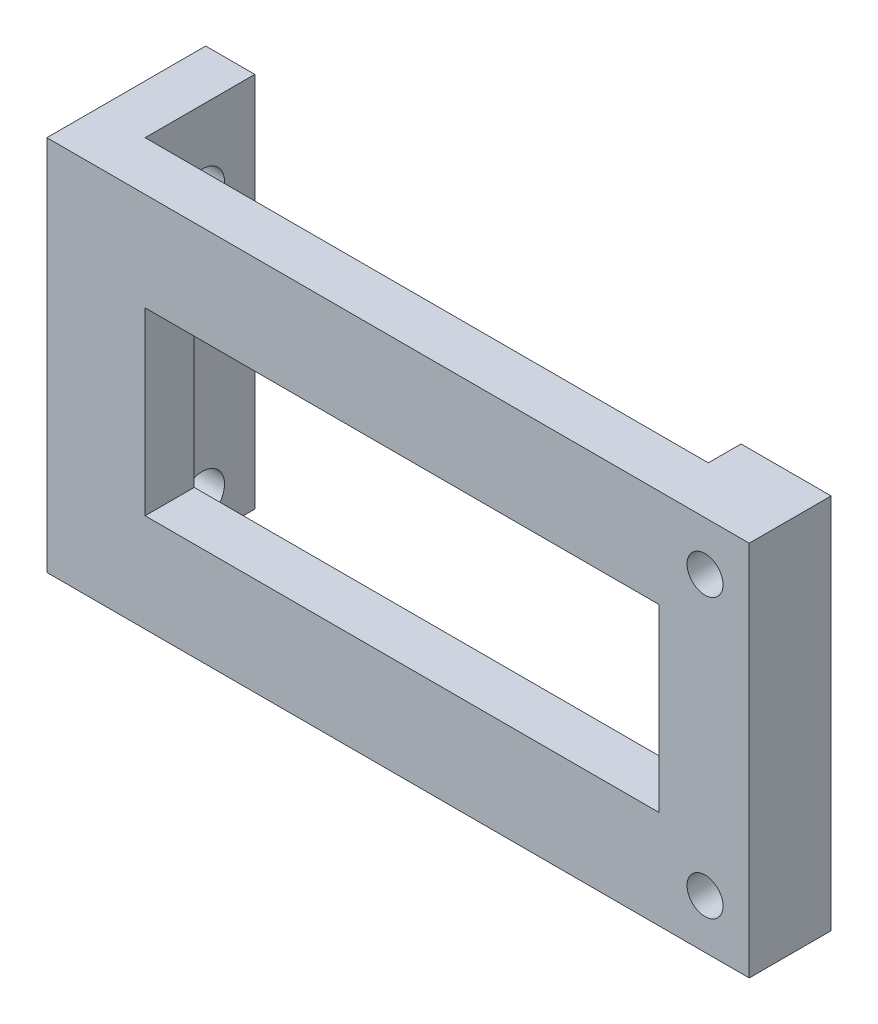
SolidWorks part; units mm, degrees
ref_plane "Front Plane" through (0, 0, 0) normal (0, 0, 1) x (1, 0, 0)
ref_plane "Top Plane" through (0, 0, 0) normal (0, 1, 0) x (1, 0, 0)
ref_plane "Right Plane" through (0, 0, 0) normal (1, 0, 0) x (0, 0, -1)
sketch "Sketch1" plane through (0, 0, 0) normal (0, 0, 1) x (1, 0, 0)
  line L0 (-15.45, 11.5) -> (-15.45, 5.5) construction
  line L1 (21.45, 11.5) -> (-21.45, 11.5)
  line L2 (21.45, 11.5) -> (21.45, -11.5)
  line L3 (21.45, -11.5) -> (-21.45, -11.5)
  line L4 (-21.45, 11.5) -> (-21.45, -11.5)
  line L5 (21.45, 11.5) -> (-21.45, -11.5) construction
  line L6 (21.45, -11.5) -> (-21.45, 11.5) construction
  line L7 (-21.45, 11.5) -> (-18.45, 11.5)
  line L8 (-21.45, 11.5) -> (-21.45, -11.5)
  line L9 (-21.45, -11.5) -> (-18.45, -11.5)
  line L10 (-18.45, 11.5) -> (-18.45, -11.5)
  line L11 (21.45, 11.5) -> (15.95, 11.5)
  line L12 (21.45, 11.5) -> (21.45, -11.5)
  line L13 (21.45, -11.5) -> (15.95, -11.5)
  line L14 (15.95, 11.5) -> (15.95, -11.5)
  line L15 (-15.45, 5.5) -> (15.95, 5.5)
  line L16 (-15.45, 5.5) -> (-15.45, -5.5)
  line L17 (-15.45, -5.5) -> (15.95, -5.5)
  line L18 (15.95, 5.5) -> (15.95, -5.5)
  line L19 (-15.45, 5.5) -> (-21.45, 5.5) construction
  line L20 (-15.45, -5.5) -> (-15.45, -11.5) construction
  circle A0 centre (18.75, -8.5) radius 1.1
  circle A1 centre (18.75, 8.5) radius 1.1
  point P0 (0, 0)
  dimension "D1" = 2.2
  dimension "D2" = 3
  dimension "D3" = 17
  dimension "D4" = 3
  dimension "D5" = 5.5
  dimension "D6" = 2.8
  dimension "D7" = 40.2
  dimension "D8" = 3
  dimension "D9" = 6
extrude "Boss-Extrude1" add sketch "Sketch1" against normal blind 3 contours L14 L1 L10 L3 region at (15.5362, 8.5, 0)
extrude "Boss-Extrude2" add sketch "Sketch1<3>" against normal blind 5 contours L1 L14 L3 L2 A1 A0 region at (18.6968, 0, 0)
sketch "Sketch1<3>" plane through (0, 0, 0) normal (0, 0, 1) x (1, 0, 0) same geometry as "Sketch1"
extrude "Boss-Extrude3" add sketch "Sketch1<4>" against normal blind 9.7 contours L10 L1 L4 L3 region at (-19.95, 0, 0)
sketch "Sketch1<4>" plane through (0, 0, 0) normal (0, 0, 1) x (1, 0, 0) same geometry as "Sketch1"
sketch "Sketch2" plane through (-21.45, 0, 0) normal (-1, 0, 0) x (0, 0, 1)
  line L1 (0, 11.5) -> (0, -11.5) construction
  circle A0 centre (-6.5, 6.75) radius 1.35
  dimension "D1" = 2.7
  dimension "D2" = 1.75
  dimension "D3" = 6.5
extrude "Cut-Extrude1" cut sketch "Sketch2" against normal up to surface (3 mm away) up to face at (-18.45, 0, -6.35)
pattern_linear "LPattern1" count 2 spacing 16 along (0, -1, 0) of "Cut-Extrude1"
